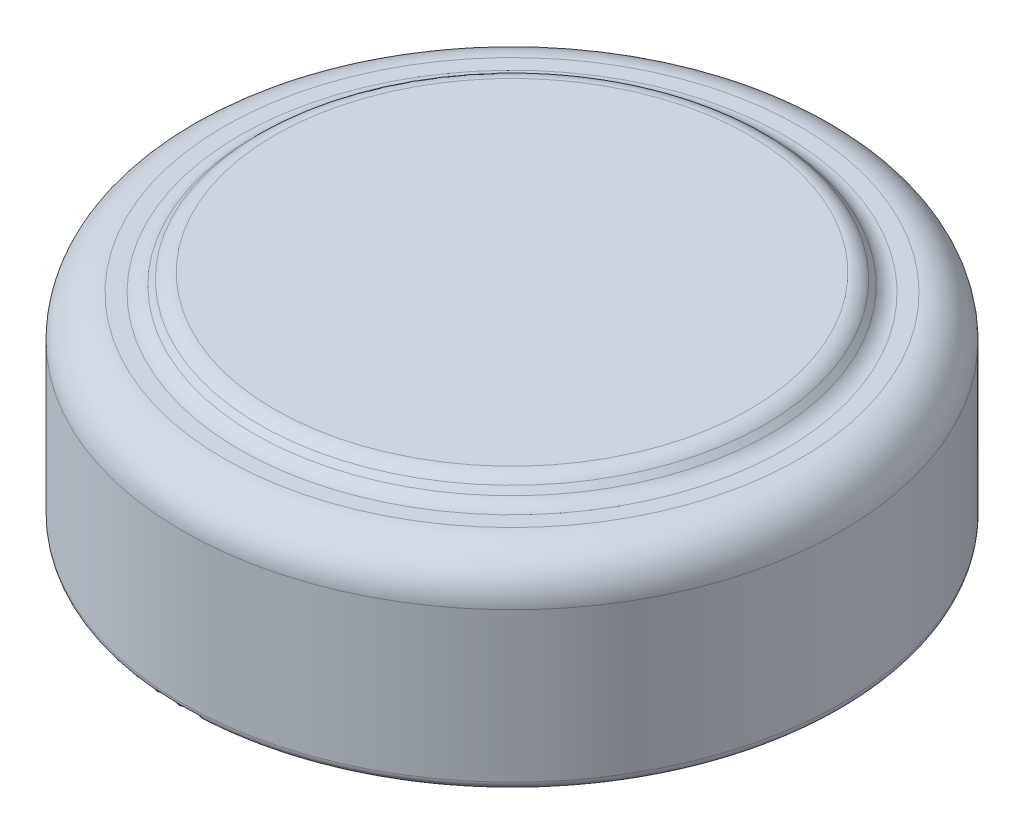
SolidWorks part; units mm, degrees
ref_plane "Front Plane" through (0, 0, 0) normal (0, 0, 1) x (1, 0, 0)
ref_plane "Top Plane" through (0, 0, 0) normal (0, 1, 0) x (1, 0, 0)
ref_plane "Right Plane" through (0, 0, 0) normal (1, 0, 0) x (0, 0, -1)
sketch "Sketch1" plane through (0, 0, 0) normal (0, 0, 1) x (1, 0, 0)
  line L0 (0, 0) -> (-3.85, 0)
  line L1 (-3.95, 0.1) -> (-3.95, 1.89)
  line L2 (-2.8464, 2.6) -> (0, 2.6)
  line L3 (0, 2.6) -> (0, 0)
  line L4 (-3.0232, 2.5268) -> (-3.0868, 2.4632)
  line L7 (-3.45, 2.39) -> (-3.2636, 2.39)
  arc A0 (-3.95, 1.89) -> (-3.45, 2.39) centre (-3.45, 1.89) cw
  arc A1 (-3.2636, 2.39) -> (-3.0868, 2.4632) centre (-3.2636, 2.64) ccw
  arc A2 (-2.8464, 2.6) -> (-3.0232, 2.5268) centre (-2.8464, 2.35) ccw
  arc A3 (-3.85, 0) -> (-3.95, 0.1) centre (-3.85, 0.1) cw
  point P9 (-3.95, 2.39)
  point P12 (-3.16, 2.39)
  point P14 (-2.95, 2.6)
  point P17 (-3.95, 0)
  dimension "D6" = 0.5
  dimension "D7" = 0.25
  dimension "D8" = 0.1
  dimension "D1" = 3.95
  dimension "D2" = 2.6
  dimension "D3" = 3.16
  dimension "D4" = 2.39
  dimension "D5" = 45
revolve "Revolve1" add sketch "Sketch1" angle 360 about L3
sketch "Sketch2" plane through (0, 0, 0) normal (0, -1, 0) x (1, 0, 0)
  line L0 (0.25, 0.25) -> (1.5, 0.25)
  line L1 (-0.25, 1.5) -> (0.25, 1.5)
  line L2 (-0.25, 1.5) -> (-0.25, 0.25)
  line L3 (-0.25, -1.5) -> (0.25, -1.5)
  line L4 (0.25, 1.5) -> (0.25, 0.25)
  line L5 (-1.5, 0.25) -> (-0.25, 0.25)
  line L6 (-1.5, 0.25) -> (-1.5, -0.25)
  line L7 (-1.5, -0.25) -> (-0.25, -0.25)
  line L8 (1.5, 0.25) -> (1.5, -0.25)
  line L9 (0.25, -0.25) -> (1.5, -0.25)
  line L10 (0.25, -0.25) -> (0.25, -1.5)
  line L11 (-0.25, -0.25) -> (-0.25, -1.5)
  circle A0 centre (0, 0) radius 2.5 construction
  text T0 "                     SR59" font "Century Gothic" height 1
  dimension "D1" = 5
  dimension "D2" = 0.5
  dimension "D3" = 0.25
  dimension "D4" = 0.25
  dimension "D5" = 0.5
  dimension "D6" = 3
  dimension "D7" = 1.5
  dimension "D8" = 1.5
  dimension "D9" = 3
wrap "Wrap1" sketch "Sketch2" wrap type scribe source sketch "Sketch2" face at (-3.85, 0, 0)
